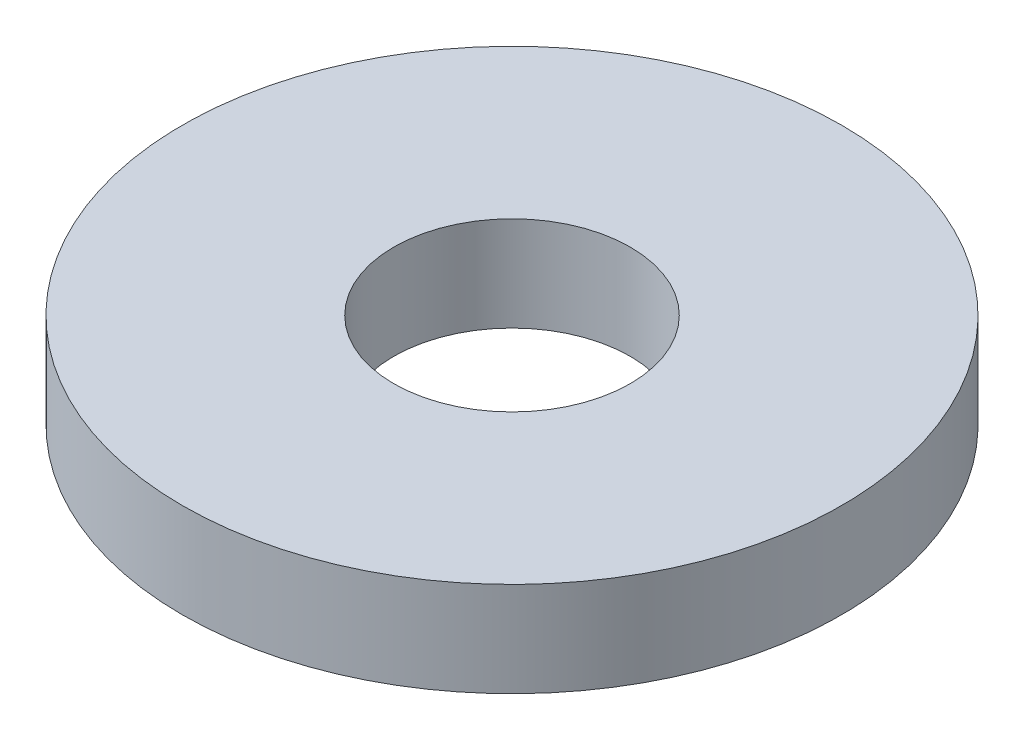
SolidWorks part; units mm, degrees
ref_plane "Front Plane" through (0, 0, 0) normal (0, 0, 1) x (1, 0, 0)
ref_plane "Top Plane" through (0, 0, 0) normal (0, 1, 0) x (1, 0, 0)
ref_plane "Right Plane" through (0, 0, 0) normal (1, 0, 0) x (0, 0, -1)
sketch "Sketch1" plane through (0, 0, 0) normal (0, 1, 0) x (1, 0, 0)
  circle A0 centre (0, 0) radius 97.5
  dimension "FLANGE_OD" = 195
extrude "Boss-Extrude1" add sketch "Sketch1" along normal blind 28
sketch "Sketch2" plane through (0, 0, 0) normal (0, 1, 0) x (1, 0, 0)
  circle A0 centre (0, 0) radius 35
  dimension "BORE_D" = 70
extrude "Cut-Extrude1" cut sketch "Sketch2" along normal through all
sketch "Sketch3" plane through (0, 28, 0) normal (0, 1, 0) x (1, 0, 0)
  circle A0 centre (0, 0) radius 26.5009 construction
  circle A1 centre (-26.5009, 0) radius 2.7274
  dimension "BOLT_D" = 5.4549
  dimension "BOLT_PCD" = 53.0018
extrude "Cut-Extrude2" cut sketch "Sketch3" against normal blind 18.5224 rebuild error yes
pattern_circular "CirPattern1" count 4 over 360 rebuild error yes
